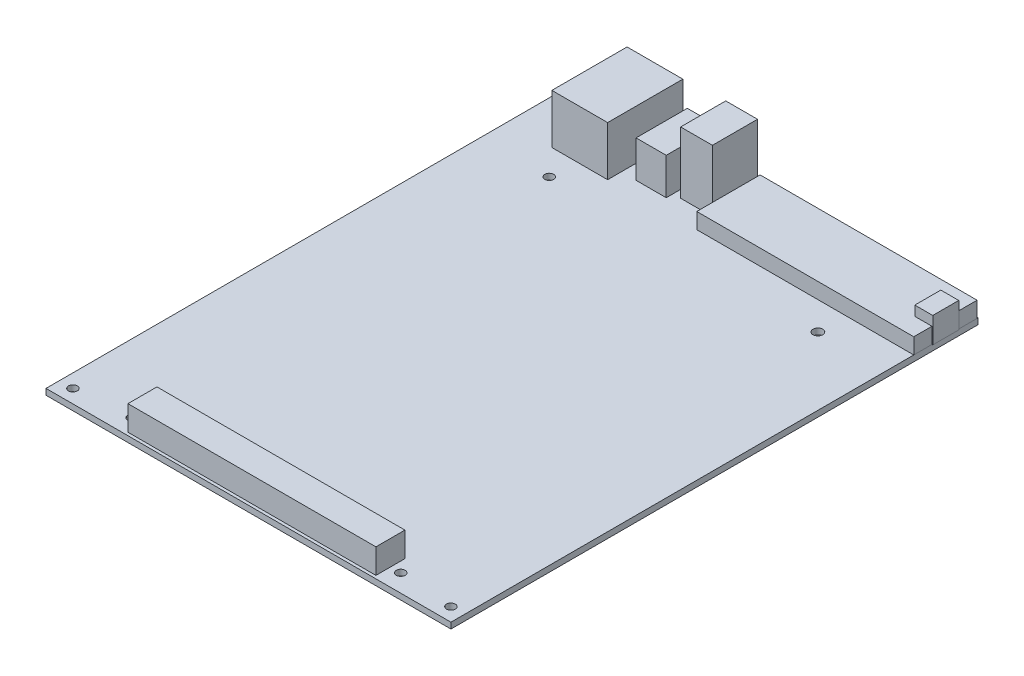
SolidWorks part; units mm, degrees
ref_plane "Front Plane" through (0, 0, 0) normal (0, 0, 1) x (1, 0, 0)
ref_plane "Top Plane" through (0, 0, 0) normal (0, 1, 0) x (1, 0, 0)
ref_plane "Right Plane" through (0, 0, 0) normal (1, 0, 0) x (0, 0, -1)
sketch "Sketch1" plane through (0, 0, 0) normal (0, 1, 0) x (1, 0, 0)
  line L0 (0.0995, 149.0448) -> (0.0995, -0.0532)
  line L1 (0.0995, -0.0532) -> (114.6535, -0.0532)
  line L2 (114.6535, -0.0532) -> (114.6535, 149.0448)
  line L3 (114.6535, 149.0448) -> (0.0995, 149.0448)
  circle A0 centre (3.9095, 145.2348) radius 1.25
  circle A1 centre (19.4539, 122.9468) radius 1.25
  circle A2 centre (95.4526, 122.9468) radius 1.3792
  circle A3 centre (3.9095, 3.7568) radius 1.25
  circle A4 centre (19.4539, 4.9468) radius 1.25
  circle A5 centre (95.4526, 4.9468) radius 1.25
  circle A6 centre (110.8435, 3.7568) radius 1.25
  point P2 (3.9095, 145.2348)
  point P4 (19.4539, 122.9468)
  point P6 (95.4526, 122.9468)
  point P7 (3.9095, 3.7568)
  point P8 (19.4539, 4.9468)
  point P9 (95.4526, 4.9468)
  point P10 (110.8435, 3.7568)
  point P25 (0, 0)
extrude "Boss-Extrude1" add sketch "Sketch1" along normal blind 1.69
sketch "Sketch2" plane through (0, 1.69, 0) normal (0, 1, 0) x (1, 0, 0)
  line L0 (114.6532, 130.8719) -> (53.2701, 130.8719)
  line L1 (114.6532, 130.8719) -> (114.6532, 148.7906)
  line L2 (114.6532, 148.7906) -> (53.2701, 148.7906)
  line L3 (0.0992, 149.0446) -> (0.0992, -0.0534) construction
  line L4 (0.0992, -0.0534) -> (114.6532, -0.0534) construction
  line L5 (114.6532, -0.0534) -> (114.6532, 149.0446) construction
  line L6 (114.6532, 149.0446) -> (0.0992, 149.0446) construction
  line L7 (53.2701, 130.8719) -> (53.2701, 148.7906)
  line L8 (109.8001, 143.3756) -> (114.8771, 143.3756)
  line L9 (109.8001, 143.3756) -> (109.8001, 136.0206)
  line L10 (109.8001, 136.0206) -> (114.8771, 136.0206)
  line L11 (114.8771, 143.3756) -> (114.8771, 136.0206)
  line L12 (12.6383, 151.7873) -> (28.4173, 151.7873)
  line L13 (12.6383, 151.7873) -> (12.6383, 130.5074)
  line L14 (12.6383, 130.5074) -> (28.4173, 130.5074)
  line L15 (28.4173, 151.7873) -> (28.4173, 130.5074)
  line L16 (32.5959, 148.8795) -> (41.1227, 148.8795)
  line L17 (32.5959, 148.8795) -> (32.5959, 134.3768)
  line L18 (32.5959, 134.3768) -> (41.1227, 134.3768)
  line L19 (41.1227, 148.8795) -> (41.1227, 134.3768)
  line L20 (92.5806, 9.0017) -> (22.4284, 9.0017)
  line L21 (92.5806, 9.0017) -> (92.5806, 0.7934)
  line L22 (92.5806, 0.7934) -> (22.4284, 0.7934)
  line L23 (22.4284, 9.0017) -> (22.4284, 0.7934)
  circle A0 centre (3.9092, 145.2346) radius 1.25 construction
  circle A1 centre (19.4537, 122.9466) radius 1.25 construction
  circle A2 centre (95.4524, 122.9466) radius 1.25 construction
  circle A3 centre (3.9092, 3.7566) radius 1.25 construction
  circle A4 centre (19.4537, 4.9466) radius 1.25 construction
  circle A5 centre (95.4524, 4.9466) radius 1.25 construction
  circle A6 centre (110.8432, 3.7566) radius 1.25 construction
  point P2 (3.9092, 145.2346)
  point P4 (19.4537, 122.9466)
  point P6 (95.4524, 122.9466)
  point P7 (3.9092, 3.7566)
  point P8 (19.4537, 4.9466)
  point P9 (95.4524, 4.9466)
  point P10 (110.8432, 3.7566)
extrude "Boss-Extrude2" add sketch "Sketch2" along normal blind 14 contours L12 L15 L14 L13
extrude "Boss-Extrude3" add sketch "Sketch2<3>" along normal blind 7 contours L20 L23 L22 L21 region at (57.5045, 1.69, -4.8975)
sketch "Sketch2<3>" plane through (0, 1.69, 0) normal (0, 1, 0) x (1, 0, 0) same geometry as "Sketch2"
extrude "Boss-Extrude4" add sketch "Sketch2<4>" along normal blind 10.4 contours L19 L16 L17 L18 region at (36.8593, 1.69, -141.6282)
sketch "Sketch2<4>" plane through (0, 1.69, 0) normal (0, 1, 0) x (1, 0, 0) same geometry as "Sketch2"
sketch "Sketch3" plane through (0, 0, -149.0448) normal (0, 0, -1) x (-1, 0, 0)
  line L0 (-114.8303, 8.6206) -> (-114.9303, 5.8616) construction
  line L1 (-40.9961, 12.3662) -> (-40.9961, 1.9662) construction
  line L2 (-40.9961, 1.9662) -> (-32.5961, 1.9662) construction
  line L3 (-32.5961, 1.9662) -> (-32.5961, 12.3662) construction
  line L4 (-32.5961, 12.3662) -> (-40.9961, 12.3662) construction
  line L5 (-52.2843, 1.6662) -> (-43.2923, 1.6662)
  line L6 (-43.2923, 1.6662) -> (-43.2923, 19.1672)
  line L7 (-43.2923, 19.1672) -> (-52.2843, 19.1672)
  line L8 (-52.2843, 19.1672) -> (-52.2843, 1.6662)
  line L9 (-114.6535, 0) -> (-0.0995, 0) construction
  line L10 (-0.0995, 0) -> (-0.0995, 1.6916) construction
  line L11 (-0.0995, 1.6916) -> (-114.6535, 1.6916) construction
  line L12 (-114.6535, 1.6916) -> (-114.6535, 0) construction
  line L13 (-53.2703, 6.0348) -> (-114.2303, 6.0348) construction
  line L14 (-114.2303, 6.0348) -> (-114.2303, 4.4648) construction
  line L15 (-114.2303, 4.4648) -> (-53.2703, 4.4648) construction
  line L16 (-53.2703, 4.4648) -> (-53.2703, 6.0348) construction
  line L17 (-28.1516, 1.865) -> (-27.9006, 1.865) construction
  line L18 (-27.9006, 1.865) -> (-13.194, 1.865) construction
  line L19 (-13.194, 1.865) -> (-12.9708, 1.865) construction
  line L20 (-12.9708, 1.865) -> (-12.9708, 14.691) construction
  line L21 (-12.9708, 14.691) -> (-28.1516, 14.691) construction
  line L22 (-28.1516, 14.691) -> (-28.1516, 1.865) construction
  point P24 (0, 0)
  point P25 (0, 0)
extrude "Boss-Extrude5" add sketch "Sketch2<5>" along normal blind 4.46 separate body contours L10 L9 L8 L1 L2 L7 L0 region at (83.0136, 1.69, -139.8357)
sketch "Sketch2<5>" plane through (0, 1.69, 0) normal (0, 1, 0) x (1, 0, 0) same geometry as "Sketch2"
extrude "Boss-Extrude6" add sketch "Sketch2<6>" along normal blind 7.22 separate body contours L8 L11 L10 L9
sketch "Sketch2<6>" plane through (0, 1.69, 0) normal (0, 1, 0) x (1, 0, 0) same geometry as "Sketch2"
extrude "Boss-Extrude7" add sketch "Sketch3" against normal blind 12.76
